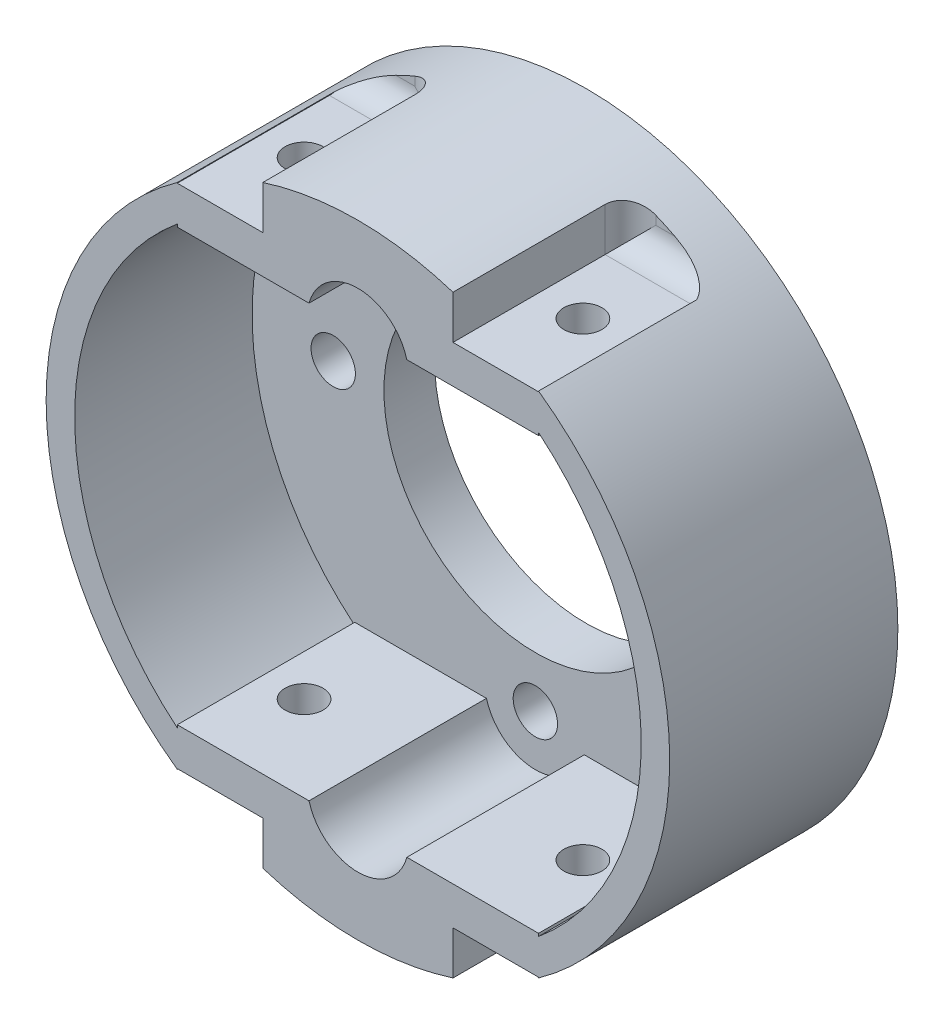
SolidWorks part; units mm, degrees
ref_plane "Front Plane" through (0, 0, 0) normal (0, 0, 1) x (1, 0, 0)
ref_plane "Top Plane" through (0, 0, 0) normal (0, 1, 0) x (1, 0, 0)
ref_plane "Right Plane" through (0, 0, 0) normal (1, 0, 0) x (0, 0, -1)
sketch "Sketch2" plane through (0, 0, 0) normal (0, 0, 1) x (1, 0, 0)
  circle A0 centre (0, 0) radius 11.95 construction
  circle A1 centre (0, 0) radius 24.6 construction
  circle A2 centre (0, 0) radius 11.95
  circle A3 centre (0, 0) radius 24.6
  circle A4 centre (-15.95, 0) radius 1.75
  circle A5 centre (0, 15.95) radius 1.75
  circle A6 centre (15.95, 0) radius 1.75
  circle A7 centre (0, -15.95) radius 1.75
  dimension "D1" = 3.5
extrude "Boss-Extrude1" add sketch "Sketch2" along normal blind 4
sketch "Sketch4" plane through (0, 0, 4) normal (0, 0, 1) x (1, 0, 0)
  line L0 (-12.1464, -17) -> (12.1464, -17) construction
  line L1 (14.25, 20) -> (-14.25, 20)
  line L2 (14.25, 20) -> (14.25, 17)
  line L3 (14.25, 17) -> (-14.25, 17)
  line L4 (-14.25, 20) -> (-14.25, 17)
  line L5 (0, 17) -> (0, 20.0524) construction
  line L6 (14.25, 18.5) -> (-14.25, 18.5) construction
  line L7 (14.25, -17) -> (-14.25, -17)
  line L8 (14.25, -17) -> (14.25, -20)
  line L9 (14.25, -20) -> (-14.25, -20)
  line L10 (-14.25, -17) -> (-14.25, -20)
  line L11 (0, -20) -> (0, -17) construction
  line L12 (14.25, -18.5) -> (-14.25, -18.5) construction
  line L13 (12.1464, 17) -> (-12.1464, 17) construction
  line L14 (14.25, 8.75) -> (14.25, 16.75) construction
  line L15 (-14.25, 16.75) -> (-14.25, 8.75) construction
  line L16 (-14.25, -8.5) -> (-14.25, -16.75) construction
  line L17 (14.25, -16.75) -> (14.25, -8.5) construction
  point P92 (0, 18.5)
  point P107 (0, -18.5)
  dimension "D2" = 3
  dimension "D1" = 3
extrude "Boss-Extrude2" add sketch "Sketch4" along normal blind 14
sketch "Sketch5" plane through (0, -20, 0) normal (0, -1, 0) x (1, 0, 0)
  circle A0 centre (-11, 11.25) radius 1.5
  circle A1 centre (11, 11.25) radius 1.5
  dimension "D2" = 3
  dimension "D1" = 3
extrude "Cut-Extrude1" cut sketch "Sketch5" against normal through all
sketch "Sketch6" plane through (0, 0, 4) normal (0, 0, 1) x (1, 0, 0)
  line L0 (0, 27.4787) -> (0, -26.2951) construction
  line L2 (7.5, 23.4288) -> (7.5, 20)
  line L4 (-7.5, 23.4288) -> (-7.5, 20)
  line L5 (0, -24.6) -> (0, -20) construction
  line L7 (-14.25, -20) -> (14.25, -20) construction
  line L8 (-7.5, -20) -> (7.5, -20)
  line L9 (14.25, 20) -> (-14.25, 20) construction
  line L10 (7.5, 20) -> (-7.5, 20)
  line L11 (-7.5, -20) -> (-7.5, -23.4288)
  line L13 (0, 20) -> (0, 29.517) construction
  line L15 (7.5, -20) -> (7.5, -23.4288)
  circle A0 centre (0, 0) radius 24.6 construction
  arc A1 (-7.5, -23.4288) -> (7.5, -23.4288) centre (0, 0) ccw
  arc A4 (7.5, 23.4288) -> (-7.5, 23.4288) centre (0, 0) ccw
  point P1 (0, 20)
  point P88 (0, -0.8165)
  dimension "D1" = 15
extrude "Boss-Extrude3" add sketch "Sketch6" along normal up to surface (14 mm away) up to face at (0, 18.5, 18)
sketch "Sketch7" plane through (0, 0, 18) normal (0, 0, 1) x (1, 0, 0)
  circle A0 centre (0, -15.95) radius 4
  circle A1 centre (0, 15.95) radius 4
  dimension "D1" = 8
  dimension "D2" = 8
extrude "Cut-Extrude2" cut sketch "Sketch7" against normal up to surface (14 mm away) up to face at (17.7, 0, 4)
fillet "Fillet1" radius 2 8 edges at (7.5, 21.7144, 4) (10.875, 20, 4) (-10.875, 20, 4) (-7.5, 21.7144, 4) (-10.875, -20, 4) (-7.5, -21.7144, 4) (7.5, -21.7144, 4) (10.875, -20, 4)
sketch "Sketch8" plane through (0, 0, 4) normal (0, 0, 1) x (1, 0, 0)
  line L0 (-14.25, -17) -> (-14.25, -20.0524) construction
  line L1 (-14.25, 20.0524) -> (-14.25, 17) construction
  line L2 (-14.25, -17.218) -> (-14.25, -20.0524)
  line L3 (-14.25, 20.0524) -> (-14.25, 17.218)
  line L4 (14.25, 17) -> (14.25, 20.0524) construction
  line L5 (14.25, -20.0524) -> (14.25, -17) construction
  line L6 (14.25, 17.218) -> (14.25, 20.0524)
  line L7 (14.25, -20.0524) -> (14.25, -17.218)
  arc A0 (-14.25, 20.0524) -> (-14.25, -20.0524) centre (0, 0) ccw construction
  arc A1 (-14.25, 20.0524) -> (-14.25, -20.0524) centre (0, 0) ccw
  arc A2 (-14.25, 17.218) -> (-14.25, -17.218) centre (0, 0) ccw
  arc A3 (-12.9466, 18.2183) -> (-12.9466, -18.2183) centre (0, 0) ccw construction
  arc A4 (14.25, -20.0524) -> (14.25, 20.0524) centre (0, 0) ccw construction
  arc A5 (14.25, -20.0524) -> (14.25, 20.0524) centre (0, 0) ccw
  arc A6 (14.25, -17.218) -> (14.25, 17.218) centre (0, 0) ccw
  arc A7 (12.9466, -18.2183) -> (12.9466, 18.2183) centre (0, 0) ccw construction
  dimension "D1" = 2.25
  dimension "D2" = 2.25
extrude "Boss-Extrude4" add sketch "Sketch8" along normal up to surface (14 mm away) up to face at (0, -19.8979, 18)
sketch "Sketch9" plane through (0, 0, 18) normal (0, 0, 1) x (1, 0, 0)
  line L0 (-9.5, -8.5) -> (-14.25, -8.5) construction
  line L1 (3.7098, -8.5) -> (20.6706, -8.5)
  line L3 (3.8004, 8.25) -> (20.7716, 8.25)
  line L5 (12.25, 8.25) -> (-12.25, 8.25) construction
  line L6 (-20.7716, 8.25) -> (-23.1754, 8.25)
  line L7 (-20.6706, -8.5) -> (-23.0848, -8.5)
  line L19 (14.25, 20.0524) -> (14.25, 20)
  line L22 (-7.5, 20) -> (-14.25, 20)
  line L23 (-14.25, 20) -> (-14.25, 20.0524)
  line L24 (-14.25, -20.0524) -> (-14.25, -20)
  line L25 (-14.25, -20) -> (-7.5, -20)
  line L26 (14.25, 20) -> (7.5, 20)
  line L27 (7.5, 20) -> (7.5, 23.4288)
  line L28 (-7.5, 23.4288) -> (-7.5, 20)
  line L42 (-7.5, -20) -> (-7.5, -23.4288)
  line L43 (7.5, -23.4288) -> (7.5, -20)
  line L44 (7.5, -20) -> (14.25, -20)
  line L45 (14.25, -20) -> (14.25, -20.0524)
  circle A0 centre (0, 0) radius 22.35 construction
  arc A1 (20.6706, -8.5) -> (20.7716, 8.25) centre (0, 0) ccw
  arc A2 (-14.25, 17.218) -> (-14.25, -17.218) centre (0, 0) ccw construction
  arc A3 (-20.7716, 8.25) -> (-20.6706, -8.5) centre (0, 0) ccw
  arc A4 (7.5, 23.4288) -> (-7.5, 23.4288) centre (0, 0) ccw
  arc A5 (-14.25, 20.0524) -> (-14.25, -20.0524) centre (0, 0) ccw
  arc A6 (-14.25, 20.0524) -> (-14.25, -20.0524) centre (0, 0) ccw
  arc A7 (-7.5, -23.4288) -> (7.5, -23.4288) centre (0, 0) ccw
  arc A12 (-14.25, 20.0524) -> (-14.25, -20.0524) centre (0, 0) ccw construction
  arc A16 (14.25, -20.0524) -> (14.25, 20.0524) centre (0, 0) ccw
  arc A17 (14.25, -20.0524) -> (14.25, 20.0524) centre (0, 0) ccw
  point P13 (-23.1754, 8.25)
  point P25 (-23.1754, -8.25)
  dimension "D1" = 0
equation "\"D2@Sketch4\"=\"D1@Sketch4\""
equation "\"D2@Sketch5\"=\"D1@Sketch5\""
equation "\"D2@Sketch7\"=\"D1@Sketch7\""
